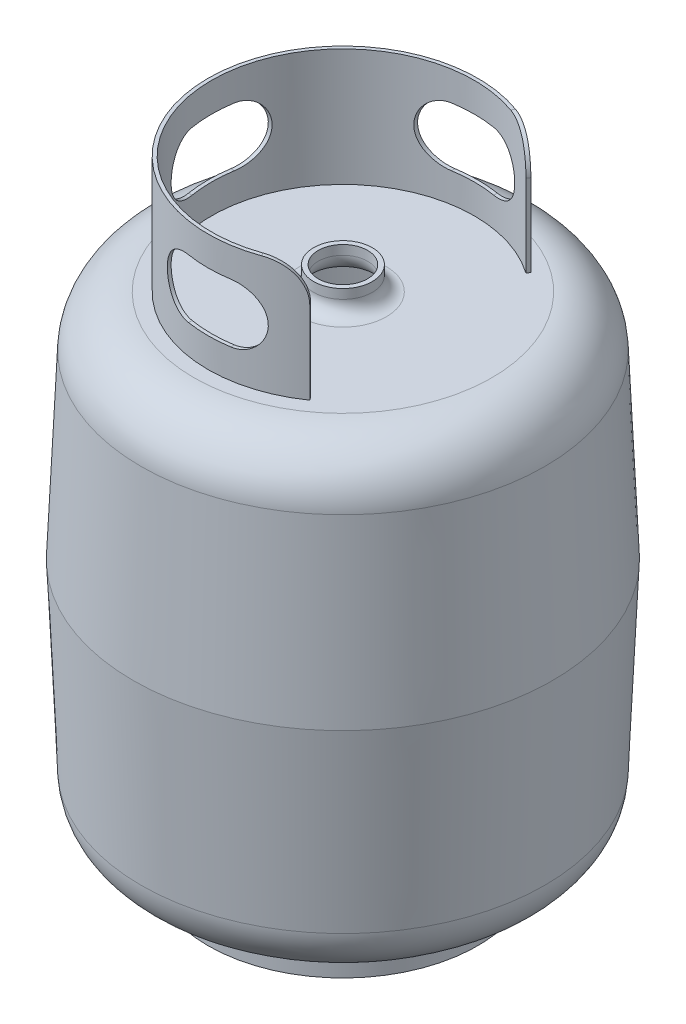
SolidWorks part; units mm, degrees
material "1060 Alloy"
ref_plane "Front Plane" through (0, 0, 0) normal (0, 0, 1) x (1, 0, 0)
ref_plane "Top Plane" through (0, 0, 0) normal (0, 1, 0) x (1, 0, 0)
ref_plane "Right Plane" through (0, 0, 0) normal (1, 0, 0) x (0, 0, -1)
sketch "Sketch1" plane through (0, 0, 0) normal (0, 1, 0) x (1, 0, 0)
  circle A0 centre (0, 0) radius 170
  dimension "D1" = 340
extrude "Boss-Extrude1" add sketch "Sketch1" along normal blind 197.5 draft 2.5 draft outward yes
sketch "Sketch2" plane through (0, 197.5, 0) normal (0, 1, 0) x (1, 0, 0)
  circle A0 centre (0, 0) radius 178.623
  circle A1 centre (0, 0) radius 178.623 construction
extrude "Boss-Extrude2" add sketch "Sketch2" along normal blind 197.5 draft 2.5
sketch "Sketch3" plane through (0, 395, 0) normal (0, 1, 0) x (1, 0, 0)
  circle A0 centre (0, 0) radius 25
  dimension "D1" = 50
extrude "Boss-Extrude3" add sketch "Sketch3" along normal blind 20
fillet "Fillet1" radius 45 2 edges at (0, 0, 170) (0, 395, 170)
fillet "Fillet2" radius 12 1 edges at (0, 395, 25)
shell "Shell1" thickness 4 removed face at (0, 415, 25)
sketch "Sketch4" plane through (0, 0, 0) normal (0, -1, 0) x (1, 0, 0)
  circle A0 centre (0, 0) radius 114.9219
  circle A1 centre (0, 0) radius 111.9219
  circle A2 centre (0, 0) radius 126.9219 construction
  dimension "D1" = 12
  dimension "D2" = 3
extrude "Boss-Extrude4" add sketch "Sketch4" along normal blind 30
sketch "Sketch5" plane through (0, 395, 0) normal (0, 1, 0) x (1, 0, 0)
  line L0 (0, 0) -> (220.7212, 0) construction
  line L1 (0, 0) -> (65.9165, 94.1385)
  line L2 (0, 0) -> (65.9165, -94.1385)
  arc A0 (65.9165, 94.1385) -> (65.9165, -94.1385) centre (0, 0) ccw
  arc A1 (64.1957, 91.681) -> (64.1957, -91.681) centre (0, 0) ccw
  circle A2 centre (0, 0) radius 126.9219 construction
  dimension "D1" = 12
  dimension "D2" = 3
  dimension "D3" = 55
  dimension "D4" = 55
extrude "Boss-Extrude5" add sketch "Sketch5" along normal blind 100 contours A1 L1 A0 L2 region at (-114.8464, 395, 0)
fillet "Fillet3" radius 30 2 edges at (65.0561, 495, 92.9098) (65.0561, 495, -92.9098)
ref_plane "Plane1" through (0, 0, 117) normal (0, 0, 1) x (1, 0, 0)
sketch "Sketch6" plane through (0, 0, 117) normal (0, 0, 1) x (1, 0, 0)
  line L0 (-18, 445) -> (18, 445) construction
  line L1 (-18, 470) -> (18, 470)
  line L2 (-18, 420) -> (18, 420)
  line L3 (37.272, 495) -> (-111.9219, 495) construction
  line L4 (0, 0) -> (0, 649.227) construction
  arc A0 (-18, 470) -> (-18, 420) centre (-18, 445) ccw
  arc A1 (18, 420) -> (18, 470) centre (18, 445) ccw
  point P2 (0, 445)
  point P12 (43, 445)
  point P13 (-43, 445)
  dimension "D2" = 86
  dimension "D1" = 50
  dimension "D3" = 50
  dimension "D4" = 18
extrude "Cut-Extrude1" cut sketch "Sketch6" against normal blind 30
pattern_circular "CirPattern1" count 3 every 90 about axis through (0, 495, 0) along (0, -1, 0) of "Cut-Extrude1"
equation "\"A\"= 340"
equation "\"B\"= 395"
equation "\"D1@Sketch1\"=\"A\""
equation "\"D1@Boss-Extrude1\"=\"B\"/2"
